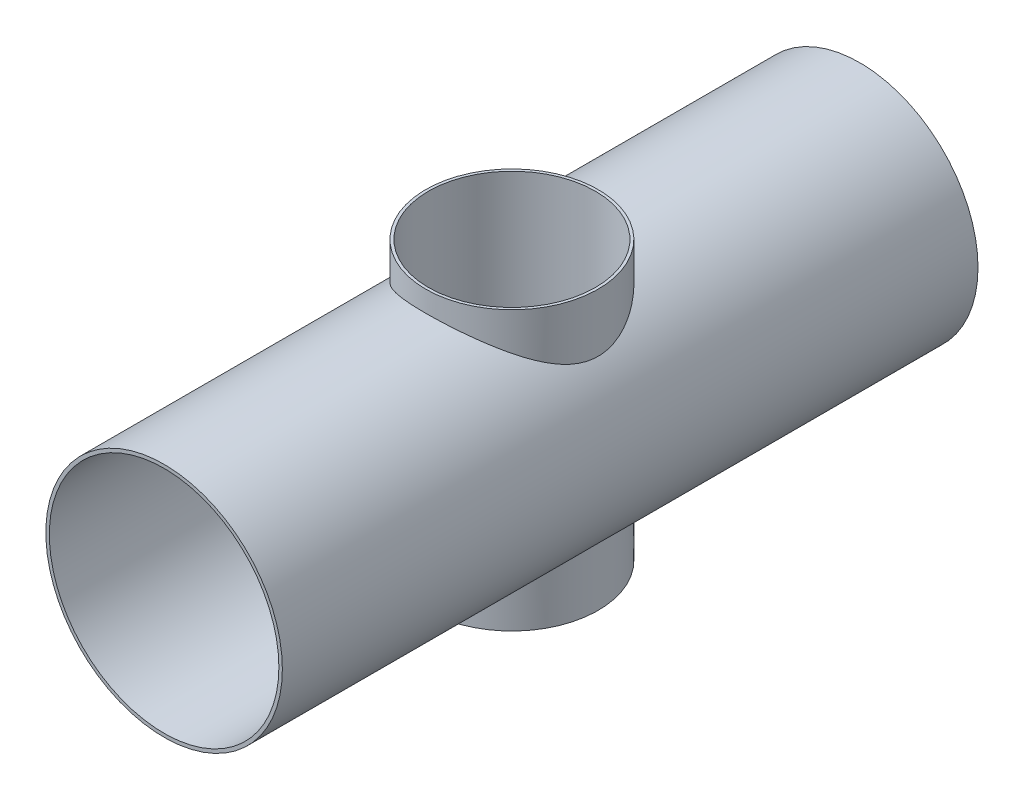
SolidWorks part; units mm, degrees
ref_plane "Front Plane" through (0, 0, 0) normal (0, 0, 1) x (1, 0, 0)
ref_plane "Top Plane" through (0, 0, 0) normal (0, 1, 0) x (1, 0, 0)
ref_plane "Right Plane" through (0, 0, 0) normal (1, 0, 0) x (0, 0, -1)
sketch "Sketch1" plane through (0, 0, 0) normal (0, 0, 1) x (1, 0, 0)
  circle A0 centre (0, 0) radius 85
  circle A1 centre (0, 0) radius 82.5
extrude "Boss-Extrude1" add sketch "Sketch1" along normal blind 500
sketch "Sketch4" plane through (0, 0, 0) normal (1, 0, 0) x (0, 0, -1)
  line L0 (0, -85) -> (0, 85) construction
  line L1 (0, -37.1098) -> (-120, -37.1098)
  line L2 (0, -37.1098) -> (0, -39.1098)
  line L3 (0, -39.1098) -> (-120, -39.1098)
  line L4 (-120, -37.1098) -> (-120, -39.1098)
  dimension "D1" = 2
  dimension "D2" = 120
extrude "Boss-Extrude2" add sketch "Sketch4" along normal up to surface and the other way up to surface contours L2 L1 L4 L3 up to face at (82.5, 0, 500) other way up to face at (82.5, 0, 500)
sketch "Sketch5" plane through (0, 0, 0) normal (0, 1, 0) x (1, 0, 0)
  line L0 (0, 0) -> (0, -500) construction
  line L1 (-85, -500) -> (85, -500) construction
  line L2 (0, -250) -> (84.7083, -250) construction
  circle A0 centre (0, -250) radius 60
  circle A1 centre (0, -250) radius 62
extrude "Boss-Extrude3" add sketch "Sketch5" along normal blind 100 and the other way blind 100
sketch "Sketch6" plane through (0, 0, 0) normal (0, 1, 0) x (1, 0, 0)
  circle A0 centre (0, -250) radius 60
extrude "Cut-Extrude1" cut sketch "Sketch6" against normal blind 100 and the other way blind 100
